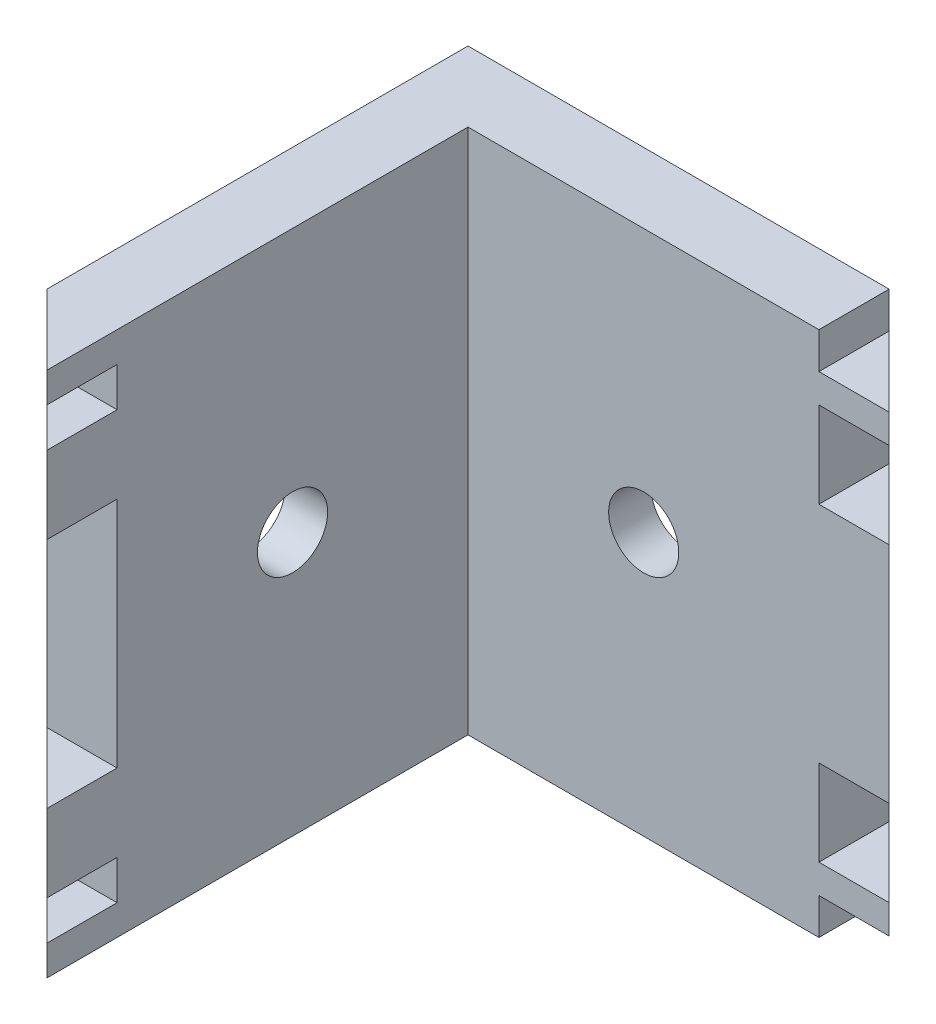
SolidWorks part; units mm, degrees
ref_plane "Front Plane" through (0, 0, 0) normal (0, 0, 1) x (1, 0, 0)
ref_plane "Top Plane" through (0, 0, 0) normal (0, 1, 0) x (1, 0, 0)
ref_plane "Right Plane" through (0, 0, 0) normal (1, 0, 0) x (0, 0, -1)
sketch "Sketch1" plane through (0, 0, 0) normal (0, 1, 0) x (1, 0, 0)
  line L1 (0, 0) -> (30.48, 0)
  line L2 (0, 0) -> (0, 30.48)
  line L5 (0, 30.48) -> (-5.08, 30.48)
  line L6 (-5.08, 30.48) -> (-5.08, -5.08)
  line L7 (30.48, -5.08) -> (-5.08, -5.08)
  line L8 (30.48, 0) -> (30.48, -5.08)
extrude "Boss-Extrude1" add sketch "Sketch1" along normal blind 31.75 and the other way blind 6.35
move or copy body "Body-Move/Copy1" bodies to move or copy 101 copy no rotation origin (-5.08, 0, 5.08) rotation axis (0, -1, 0) rotation angle 90
move or copy body "Body-Move/Copy2" bodies to move or copy 110 copy no translate (0, 0, -25.4)
move or copy body "Body-Move/Copy3" bodies to move or copy 111 copy no translate (0, 0, -25.4)
sketch "Sketch24" plane through (0, 0, 0) normal (1, 0, 0) x (0, 0, -1)
  line L0 (10.16, 12.7) -> (40.64, 12.7) construction
  line L1 (15.24, 26.73) -> (10.16, 26.73)
  line L2 (40.64, 31.75) -> (40.64, -6.35) construction
  line L4 (15.24, 26.73) -> (15.24, 29.57)
  line L5 (15.24, 29.57) -> (10.16, 29.57)
  line L6 (10.16, 26.73) -> (10.16, 29.57)
  line L7 (15.24, 26.73) -> (10.16, 29.57) construction
  line L8 (15.24, 29.57) -> (10.16, 26.73) construction
  line L18 (15.24, 4.272) -> (10.16, 4.272)
  line L19 (15.24, 4.272) -> (15.24, 21.128)
  line L20 (15.24, 21.128) -> (10.16, 21.128)
  line L21 (10.16, 4.272) -> (10.16, 21.128)
  line L22 (15.24, 4.272) -> (10.16, 21.128) construction
  line L23 (15.24, 21.128) -> (10.16, 4.272) construction
  line L26 (10.16, 28.15) -> (40.64, 28.15) construction
  line L27 (10.16, -2.75) -> (40.64, -2.75) construction
  line L28 (10.16, -6.35) -> (40.64, -6.35) construction
  line L29 (10.16, 31.75) -> (40.64, 31.75) construction
  line L30 (10.16, -6.35) -> (10.16, 31.75) construction
  line L32 (15.24, -4.17) -> (10.16, -4.17)
  line L33 (15.24, -4.17) -> (15.24, -1.33)
  line L34 (15.24, -1.33) -> (10.16, -1.33)
  line L35 (10.16, -4.17) -> (10.16, -1.33)
  line L36 (15.24, -4.17) -> (10.16, -1.33) construction
  line L37 (15.24, -1.33) -> (10.16, -4.17) construction
  point P4 (12.7, 12.7)
  point P10 (12.7, -2.75)
  dimension "D1" = 3.6
  dimension "D2" = 3.6
  dimension "D3" = 2.84
  dimension "D4" = 2.84
  dimension "D5" = 16.856
extrude "Cut-Extrude4" cut sketch "Sketch24" against normal through all
sketch "Sketch26" plane through (0, 0, -40.64) normal (0, 0, 1) x (1, 0, 0)
  line L0 (30.48, 1.4825) -> (0, 1.4825) construction
  line L1 (0, 31.75) -> (0, -6.35) construction
  line L2 (30.48, 23.9175) -> (0, 23.9175) construction
  line L4 (30.48, 31.75) -> (30.48, -6.35) construction
  line L8 (30.48, 27.03) -> (25.4, 27.03)
  line L9 (30.48, 29.12) -> (25.4, 29.12)
  line L10 (0, 31.75) -> (30.48, 31.75) construction
  line L12 (0, -6.35) -> (30.48, -6.35) construction
  line L13 (30.48, 29.12) -> (30.48, 31.75)
  line L14 (30.48, 31.75) -> (25.4, 31.75)
  line L15 (25.4, 29.12) -> (25.4, 31.75)
  line L16 (30.48, 27.03) -> (30.48, 20.805)
  line L17 (30.48, 20.805) -> (25.4, 20.805)
  line L18 (25.4, 27.03) -> (25.4, 20.805)
  line L19 (30.48, 4.595) -> (25.4, 4.595)
  line L20 (30.48, 4.595) -> (30.48, -1.63)
  line L21 (30.48, -1.63) -> (25.4, -1.63)
  line L22 (25.4, 4.595) -> (25.4, -1.63)
  line L23 (30.48, -3.72) -> (25.4, -3.72)
  line L24 (30.48, -3.72) -> (30.48, -6.35)
  line L25 (30.48, -6.35) -> (25.4, -6.35)
  line L26 (25.4, -3.72) -> (25.4, -6.35)
  dimension "D1" = 7.8325
  dimension "D2" = 7.8325
  dimension "D3" = 2.63
  dimension "D4" = 6.225
  dimension "D5" = 6.225
  dimension "D6" = 2.63
extrude "Cut-Extrude5" cut sketch "Sketch26" against normal through all
chamfer "Chamfer1" distance 5.08 angle 45 4 edges at (-5.08, -5.26, -10.16) (-5.08, 1.471, -10.16) (-5.08, 23.929, -10.16) (-5.08, 30.66, -10.16)
chamfer "Chamfer2" distance 5.08 angle 45 3 edges at (30.48, -2.675, -45.72) (30.48, 12.7, -45.72) (30.48, 28.075, -45.72)
sketch "Sketch28" plane through (-5.08, 0, 0) normal (-1, 0, 0) x (0, 0, 1)
  line L0 (-21.8553, 8.1325) -> (-34.0247, 8.1325)
  line L10 (-21.8553, 8.1325) -> (-21.8553, 17.2323)
  line L19 (-21.8553, 17.2323) -> (-34.0247, 17.2323)
  line L20 (-34.0247, 8.1325) -> (-34.0247, 17.2323)
  line L21 (-21.8553, 8.1325) -> (-34.0247, 17.2323) construction
  line L22 (-21.8553, 17.2323) -> (-34.0247, 8.1325) construction
  point P0 (-27.94, 12.6824)
  point P4 (-27.94, 12.6824)
sketch "Sketch29" plane through (0, 0, -45.72) normal (0, 0, -1) x (-1, 0, 0)
  line L19 (-6.658, 8.182) -> (-18.742, 8.182)
  line L20 (-6.658, 8.182) -> (-6.658, 17.218)
  line L21 (-6.658, 17.218) -> (-18.742, 17.218)
  line L22 (-18.742, 8.182) -> (-18.742, 17.218)
  line L23 (-6.658, 8.182) -> (-18.742, 17.218) construction
  line L24 (-6.658, 17.218) -> (-18.742, 8.182) construction
  point P1 (-12.7, 12.7)
extrude "Cut-Extrude6" cut sketch "Sketch29" against normal blind 2
extrude "Cut-Extrude7" cut sketch "Sketch28" against normal blind 2
sketch "Sketch38" plane through (-3.08, 0, 0) normal (-1, 0, 0) x (0, 0, 1)
  circle A0 centre (-27.94, 12.7) radius 2.54
  point P4 (-27.94, 12.7)
extrude "Cut-Extrude8" cut sketch "Sketch38" against normal up to next
sketch "Sketch40" plane through (0, 0, -43.72) normal (0, 0, -1) x (-1, 0, 0)
  circle A0 centre (-12.7177, 12.7) radius 2.54
  point P4 (-12.7177, 12.7)
extrude "Cut-Extrude10" cut sketch "Sketch40" against normal up to next
sketch "Sketch41" plane through (0, 0, -43.72) normal (0, 0, -1) x (-1, 0, 0)
  line L1 (-9.3526, 16.51) -> (-7.4476, 8.89) construction
  line L2 (-9.3526, 8.89) -> (-7.4476, 16.51) construction
  line L3 (-7.4476, 8.89) -> (-7.4476, 16.51)
  line L5 (-9.3526, 16.51) -> (-7.4476, 16.51)
  line L7 (-9.3526, 8.89) -> (-9.3526, 16.51)
  line L8 (-9.3526, 8.89) -> (-7.4476, 8.89)
  line L11 (-16.0474, 8.89) -> (-17.9524, 8.89)
  line L12 (-16.0474, 8.89) -> (-16.0474, 16.51)
  line L13 (-16.0474, 16.51) -> (-17.9524, 16.51)
  line L14 (-17.9524, 8.89) -> (-17.9524, 16.51)
  line L15 (-16.0474, 8.89) -> (-17.9524, 16.51) construction
  line L16 (-16.0474, 16.51) -> (-17.9524, 8.89) construction
  point P10 (-8.4001, 12.7)
  point P17 (-16.9999, 12.7)
extrude "Cut-Extrude11" cut sketch "Sketch41" against normal blind 1.2
sketch "Sketch42" plane through (-3.08, 0, 0) normal (-1, 0, 0) x (0, 0, 1)
  line L0 (-24.5926, 16.51) -> (-22.6876, 8.89) construction
  line L5 (-24.5926, 8.89) -> (-22.6876, 16.51) construction
  line L6 (-22.6876, 8.89) -> (-22.6876, 16.51)
  line L7 (-24.5926, 16.51) -> (-22.6876, 16.51)
  line L12 (-24.5926, 8.89) -> (-24.5926, 16.51)
  line L15 (-24.5926, 8.89) -> (-22.6876, 8.89)
  line L18 (-31.2874, 8.89) -> (-33.1924, 8.89)
  line L19 (-31.2874, 8.89) -> (-31.2874, 16.51)
  line L20 (-31.2874, 16.51) -> (-33.1924, 16.51)
  line L21 (-33.1924, 8.89) -> (-33.1924, 16.51)
  line L22 (-31.2874, 8.89) -> (-33.1924, 16.51) construction
  line L23 (-31.2874, 16.51) -> (-33.1924, 8.89) construction
  point P4 (-23.6401, 12.7)
  point P5 (-32.2399, 12.7)
extrude "Cut-Extrude12" cut sketch "Sketch42" against normal blind 1.2
